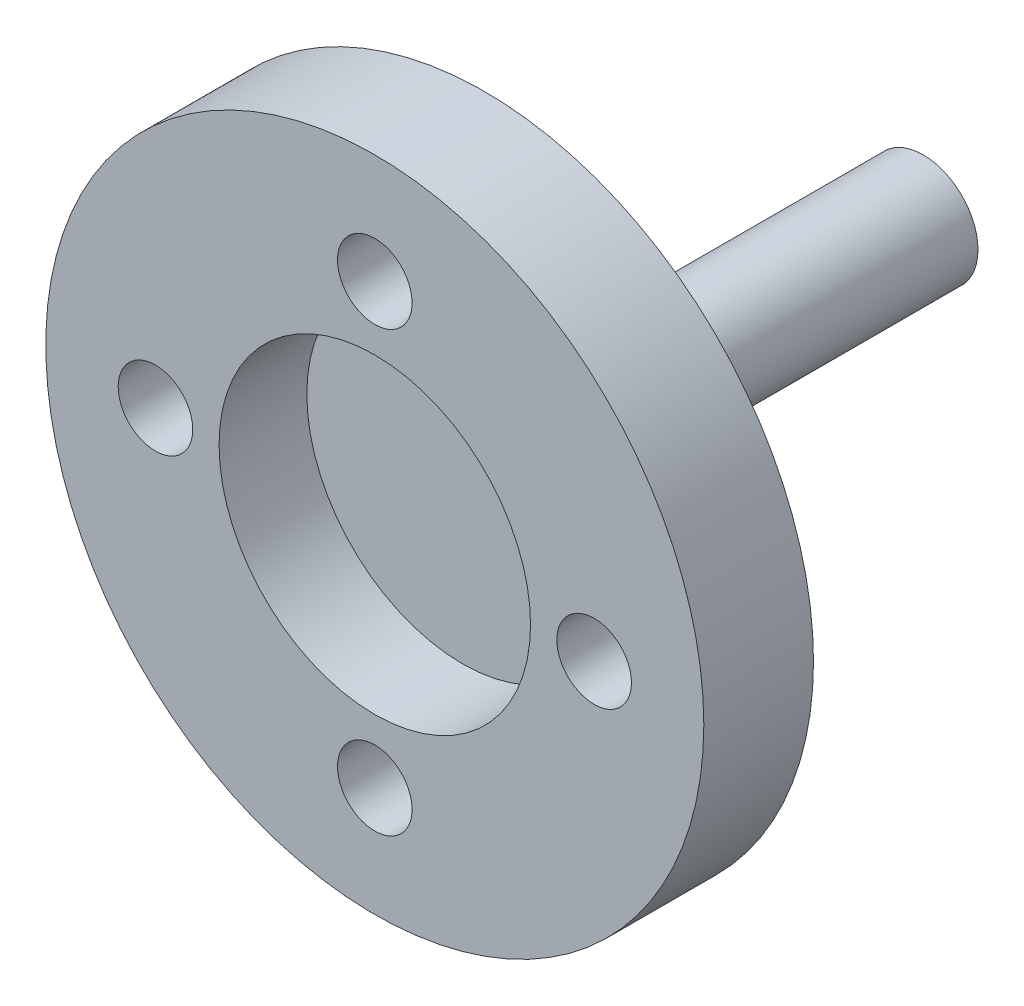
SolidWorks part; units mm, degrees
ref_plane "Спереди" through (0, 0, 0) normal (0, 0, 1) x (1, 0, 0)
ref_plane "Сверху" through (0, 0, 0) normal (0, 1, 0) x (1, 0, 0)
ref_plane "Справа" through (0, 0, 0) normal (1, 0, 0) x (0, 0, -1)
sketch "Эскиз1" plane through (0, 0, 0) normal (0, 0, 1) x (1, 0, 0)
  circle A0 centre (0, 0) radius 15
  dimension "D1" = 30
extrude "Бобышка-Вытянуть1" add sketch "Эскиз1" along normal blind 5
sketch "Эскиз2" plane through (0, 0, 5) normal (0, 0, 1) x (1, 0, 0)
  circle A0 centre (0, 0) radius 7.1
  dimension "D1" = 14.2
extrude "Вырез-Вытянуть1" cut sketch "Эскиз2" against normal blind 4
sketch "Эскиз3" plane through (0, 0, 0) normal (0, 0, -1) x (-1, 0, 0)
  circle A0 centre (0, 0) radius 2.5
  dimension "D1" = 5
extrude "Бобышка-Вытянуть2" add sketch "Эскиз3" along normal blind 20
sketch "Эскиз4" plane through (0, 0, 0) normal (0, 0, -1) x (-1, 0, 0)
  line L0 (0, 15) -> (0, -15) construction
  line L1 (15, 0) -> (-15, 0) construction
  circle A0 centre (0, 0) radius 10 construction
  circle A1 centre (0, 0) radius 15 construction
  dimension "D1" = 20
hole_wizard "Отверстие с зазором M31" positions "Эскиз6" profile "Эскиз5" hole size "M3" standard "Ansi Metric" end condition through all
sketch "Эскиз6" plane through (0, 0, 0) normal (0, 0, -1) x (-1, 0, 0)
  line L0 (0, 15) -> (0, -15) construction
  line L1 (15, 0) -> (-15, 0) construction
  circle A0 centre (0, 0) radius 10 construction
  point P0 (0, 10)
  point P6 (-10, 0)
  point P10 (0, -10)
  point P12 (10, 0)
sketch "Эскиз5" plane through (0, 10, 0) normal (1, 0, 0) x (0, 1, 0)
  line L0 (0, 0) -> (0, 5)
  line L1 (0, 5) -> (1.7, 5)
  line L2 (1.7, 5) -> (1.7, 0)
  line L5 (1.7, 0) -> (0, 0)
  line L11 (0, -6.35) -> (0, 107.95) construction
  dimension "Диаметр сквозного отверстия" = 3.4
  dimension "Глубина сквозного отверстия" = 5
